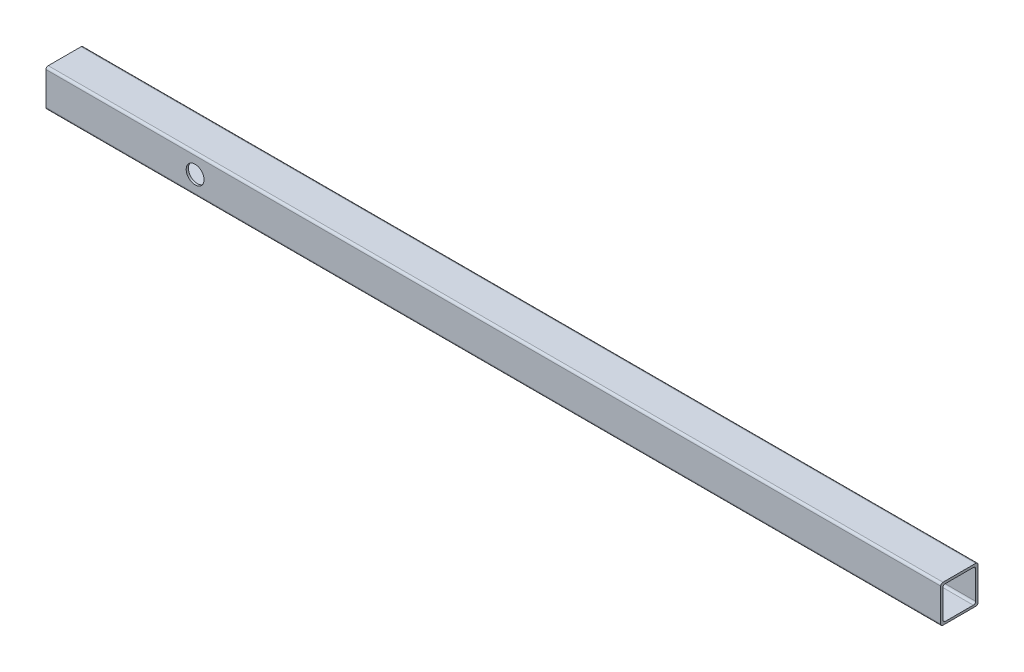
SolidWorks part; units mm, degrees
ref_plane "Front Plane" through (0, 0, 0) normal (0, 0, 1) x (1, 0, 0)
ref_plane "Top Plane" through (0, 0, 0) normal (0, 1, 0) x (1, 0, 0)
ref_plane "Right Plane" through (0, 0, 0) normal (1, 0, 0) x (0, 0, -1)
sketch "Sketch2" plane through (0, 0, 0) normal (1, 0, 0) x (0, 0, -1)
  line L1 (0.762, 0) -> (11.938, 0)
  line L2 (0, 0.762) -> (0, 11.938)
  line L3 (0.762, 12.7) -> (11.938, 12.7)
  line L4 (12.7, 0.762) -> (12.7, 11.938)
  line L5 (1.524, 0.762) -> (11.1125, 0.762)
  line L6 (0.762, 1.524) -> (0.762, 11.1125)
  line L7 (1.524, 11.8745) -> (11.1125, 11.8745)
  line L8 (11.8745, 1.524) -> (11.8745, 11.1125)
  arc A0 (11.1125, 11.8745) -> (11.8745, 11.1125) centre (11.1125, 11.1125) cw
  arc A1 (11.1125, 0.762) -> (11.8745, 1.524) centre (11.1125, 1.524) ccw
  arc A2 (1.524, 0.762) -> (0.762, 1.524) centre (1.524, 1.524) cw
  arc A3 (0.762, 11.1125) -> (1.524, 11.8745) centre (1.524, 11.1125) cw
  arc A4 (11.938, 12.7) -> (12.7, 11.938) centre (11.938, 11.938) cw
  arc A5 (11.938, 0) -> (12.7, 0.762) centre (11.938, 0.762) ccw
  arc A6 (0.762, 0) -> (0, 0.762) centre (0.762, 0.762) cw
  arc A7 (0, 11.938) -> (0.762, 12.7) centre (0.762, 11.938) cw
  point P11 (11.8745, 11.8745)
  point P14 (11.8745, 0.762)
  point P19 (0.762, 11.8745)
  point P22 (12.7, 12.7)
  point P25 (12.7, 0)
  point P28 (0, 0)
  point P31 (0, 12.7)
  dimension "D7" = 0.762
  dimension "D1" = 12.7
  dimension "D2" = 12.7
  dimension "D3" = 11.1125
  dimension "D4" = 11.1125
  dimension "D5" = 0.762
  dimension "D6" = 0.762
extrude "Boss-Extrude1" add sketch "Sketch2" along normal blind 304.8
sketch "Sketch3" plane through (0, 0, 0) normal (0, 0, 1) x (1, 0, 0)
  line L0 (0, 11.938) -> (0, 0.762) construction
  line L1 (304.8, 12.7) -> (0, 12.7) construction
  circle A0 centre (50.8, 6.35) radius 3.048
  dimension "D1" = 6.096
  dimension "D2" = 50.8
  dimension "D3" = 6.35
extrude "Cut-Extrude1" cut sketch "Sketch3" against normal up to surface (12.7 mm away) up to face at (152.4, 6.35, -12.7)
equation "\"shaft\"=0.5"
equation "\"D1@Sketch2\"=\"shaft\""
equation "\"D2@Sketch2\"=\"shaft\""
equation "\"IDshaft\"=0.4375"
equation "\"D3@Sketch2\"=\"IDshaft\""
equation "\"D4@Sketch2\"=\"IDshaft\""
equation "\"D3@Sketch3\"=\"shaft\"/2"
